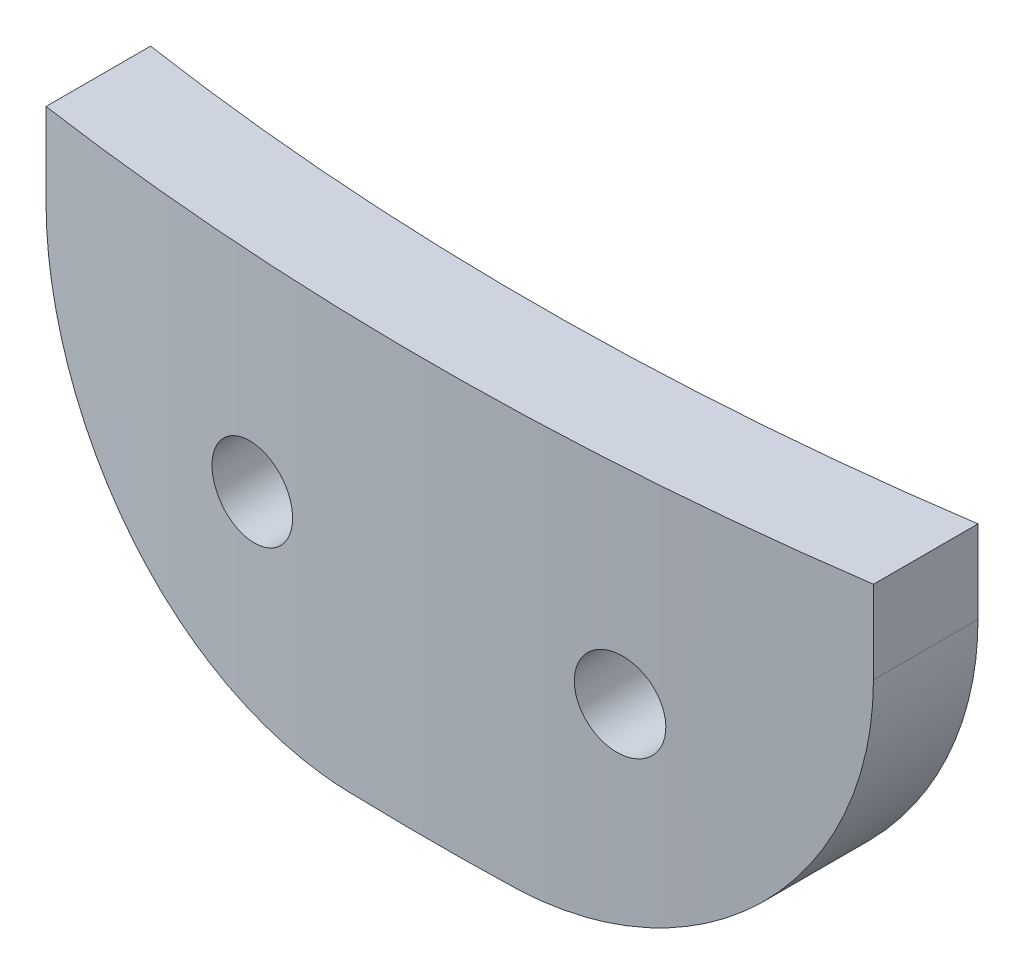
SolidWorks part; units mm, degrees
ref_plane "Front Plane" through (0, 0, 0) normal (0, 0, 1) x (1, 0, 0)
ref_plane "Top Plane" through (0, 0, 0) normal (0, 1, 0) x (1, 0, 0)
ref_plane "Right Plane" through (0, 0, 0) normal (1, 0, 0) x (0, 0, -1)
sketch "Sketch1" plane through (0, 0, 0) normal (0, 1, 0) x (1, 0, 0)
  line L0 (-12.7, -84.779) -> (-12.7, -87.9882)
  line L1 (12.7, -84.779) -> (12.7, -87.9882)
  circle A0 centre (0, 0) radius 85.725
  circle A1 centre (0, 0) radius 88.9
  dimension "D1" = 171.45
  dimension "D3" = 12.7
  dimension "D4" = 12.7
  dimension "D2" = 3.175
extrude "Boss-Extrude1" add sketch "Sketch1" along normal blind 12.7 contours L0 A1 L1 A0 region at (0, 0, 87.0027)
sketch "Sketch2" plane through (0, 0, 0) normal (0, 0, 1) x (1, 0, 0)
  line L0 (0, 12.7) -> (0, 0) construction
  line L4 (-12.7, 0) -> (12.7, 0)
  line L5 (12.7, 0) -> (12.7, 12.7)
  line L6 (12.7, 12.7) -> (-12.7, 12.7)
  line L7 (-12.7, 12.7) -> (-12.7, 0)
  line L8 (-12.7, 0) -> (12.7, 0)
  line L9 (12.7, 0) -> (12.7, 12.7)
  line L10 (12.7, 12.7) -> (-12.7, 12.7)
  line L11 (-12.7, 12.7) -> (-12.7, 0)
  circle A0 centre (-5.6444, 6.35) radius 1.3208
  dimension "D3" = 12.7
  dimension "D6" = 2.6416
  dimension "D2" = 6.35
  dimension "D5" = 5.6444
extrude "Cut-Extrude1" cut sketch "Sketch2" along normal up to surface (88.7948 mm away) contours A0 up to face at (0, 6.35, 88.4441)
mirror "Mirror1" about plane through (0, 0, 0) normal (1, 0, 0) of "Cut-Extrude1"
sketch "Sketch3" plane through (0, 0, 0) normal (0, 0, 1) x (1, 0, 0)
  line L0 (-12.7, 12.7) -> (-12.7, 0)
  line L1 (-12.7, 0) -> (12.7, 0)
  line L2 (12.7, 0) -> (12.7, 12.7)
  line L4 (-12.7, 0) -> (12.7, 0)
  line L5 (12.7, 0) -> (12.7, 12.7)
  line L6 (12.7, 12.7) -> (-12.7, 12.7)
  line L7 (-12.7, 12.7) -> (-12.7, 0)
  line L8 (-2.54, 0) -> (2.54, 0)
  line L9 (12.7, 10.16) -> (12.7, 12.7)
  line L10 (12.7, 12.7) -> (-12.7, 12.7)
  line L11 (-12.7, 12.7) -> (-12.7, 10.16)
  arc A0 (2.54, 0) -> (12.7, 10.16) centre (2.54, 10.16) ccw
  arc A1 (-2.54, 0) -> (-12.7, 10.16) centre (-2.54, 10.16) cw
  dimension "D2" = 10.16
  dimension "D1" = 0
extrude "Cut-Extrude2" cut sketch "Sketch3" along normal up to surface (87.9882 mm away) contours L1 A1 L0 | A0 L1 L2 region at (-10.4306, 2.2694, 0) region at (10.4306, 2.2694, 0) up to face at (6.9298, 6.6537, 88.6295)
equation "\"Middle Coupler Inner Daimeter\"= 6.25in"
equation "\"Middle Coupler  Wall Thickness\" = 0.25in"
equation "\"Middle Coupler Bottom Thickness\"= 0.2in"
equation "\"Bearing Rail Offset\"= 0.45in"
equation "\"3-56 UNF Tap\"= 0.089in"
equation "\"3-56 UNF Clearance\"= 0.104in"
equation "\"Ball Bearing Distance\"= 0.03in"
equation "\"TCA Outer Diameter\" = 8.625in"
equation "\"D1@Sketch1\"=\"Middle Coupler Inner Daimeter\"+0.5"
equation "\"D2@Sketch1\"=1/8"
equation "\"D3@Sketch1\"=0.5"
equation "\"D4@Sketch1\"=\"D3@Sketch1\""
equation "\"D2@Sketch2\"=\"D3@Sketch2\"/2"
equation "\"D6@Sketch2\"=\"3-56 UNF Clearance\""
equation "\"D5@Sketch2\"=\"D4@Sketch2\"/4.5"
